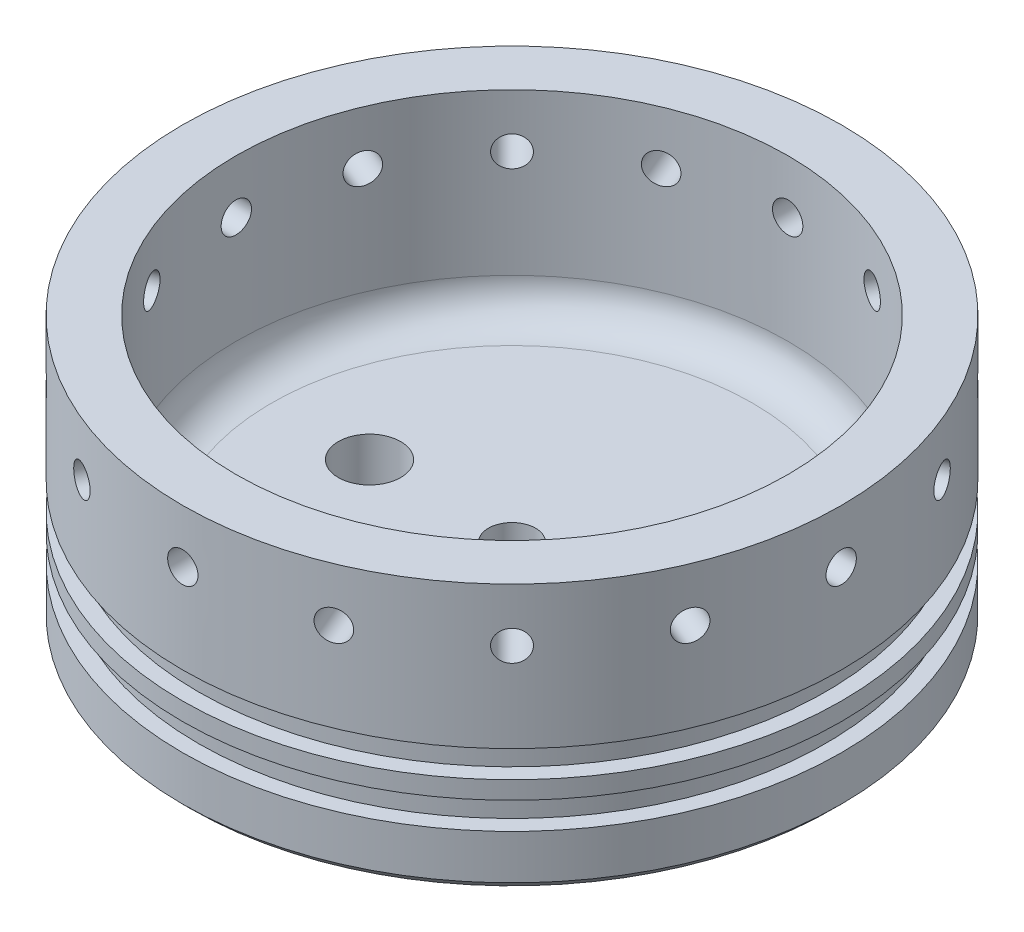
SolidWorks part; units mm, degrees
material "6061-T6 (SS)"
ref_plane "Front Plane" through (0, 0, 0) normal (0, 0, 1) x (1, 0, 0)
ref_plane "Top Plane" through (0, 0, 0) normal (0, 1, 0) x (1, 0, 0)
ref_plane "Right Plane" through (0, 0, 0) normal (1, 0, 0) x (0, 0, -1)
sketch "Sketch1" plane through (0, 0, 0) normal (0, 0, 1) x (1, 0, 0)
  line L1 (0, 0) -> (58.7375, 0)
  line L2 (58.7375, 0) -> (58.7375, 50.8) construction
  line L3 (0, 47.7012) -> (9.525, 47.7012)
  line L4 (58.7375, 0) -> (58.7375, 12.7)
  line L5 (58.7375, 12.7) -> (9.525, 12.7)
  line L6 (9.525, 12.7) -> (9.525, 47.7012)
  line L8 (0, 0) -> (0, 9.525)
  line L9 (0, 9.525) -> (2.8194, 9.525)
  line L10 (2.8194, 9.525) -> (2.8194, 14.3256)
  line L11 (2.8194, 14.3256) -> (0, 14.3256)
  line L15 (0, 14.3256) -> (0, 17.5006)
  line L16 (0, 17.5006) -> (2.8194, 17.5006)
  line L17 (2.8194, 17.5006) -> (2.8194, 22.3012)
  line L18 (2.8194, 22.3012) -> (0, 22.3012)
  line L19 (0, 22.3012) -> (0, 47.7012)
  point P13 (0, 0)
  dimension "D1" = 3.175
  dimension "D2" = 58.7375
  dimension "D3" = 12.7
  dimension "D4" = 9.525
  dimension "D5" = 4.8006
  dimension "D6" = 2.8194
  dimension "D10" = 25.4
  dimension "D11" = 9.525
revolve "Revolve1" add sketch "Sketch1" angle 360 about L2 region at (0.7567, 4.7625, 0)
ref_plane "HoleReferencePlane" through (0, 0, 58.7375) normal (0, 0, 1) x (1, 0, 0)
sketch "HoleReferencePoint" plane through (0, 0, 58.7375) normal (0, 0, 1) x (1, 0, 0)
  line L0 (107.95, 47.7012) -> (9.525, 47.7012) construction
  point P0 (58.7375, 38.1762)
  dimension "D1" = 9.525
hole_wizard "ForwardClosureHoles" positions "Sketch3" profile "Sketch5" hole size "1/4-28" standard "ANSI Inch" end condition through all
sketch "Sketch3" plane through (0, 0, 58.7375) normal (0, 0, 1) x (1, 0, 0)
  point P0 (58.7375, 38.1762)
sketch "Sketch5" plane through (58.7375, 38.1762, 58.7375) normal (1, 0, 0) x (0, -1, 0)
  line L0 (0, 0) -> (0, 117.475)
  line L1 (0, 117.475) -> (2.7051, 117.475)
  line L2 (2.7051, 117.475) -> (2.7051, 0)
  line L5 (2.7051, 0) -> (0, 0)
  line L11 (0, -6.35) -> (0, 107.95) construction
  dimension "Thru Hole Dia." = 5.4102
  dimension "Thru Hole Depth" = 117.475
sketch "Centerline" plane through (0, 0, 0) normal (0, 0, 1) x (1, 0, 0)
  line L0 (58.7375, 47.7012) -> (58.7375, 0) construction
  line L1 (117.475, 47.7012) -> (0, 47.7012) construction
  line L2 (0, 0) -> (117.475, 0) construction
pattern_circular "HolePattern" count 16 over 360 about axis through (58.7375, 47.7012, 0) along (0, -1, 0) of "ForwardClosureHoles"
ref_plane "HoleAlignmentPlane" through (0, 38.1762, 0) normal (0, 1, 0) x (1, 0, 0)
chamfer "Chamfer1" distance 1.5875 angle 45 1 edges at (58.7375, 0, -58.7375)
fillet "Fillet1" radius 6.35 1 edges at (58.7375, 12.7, -49.2125)
sketch "Sketch7" plane through (0, 0, 0) normal (0, 1, 0) x (1, 0, 0)
  line L0 (58.7375, 0) -> (84.1375, 0)
  line L2 (58.7375, 0) -> (33.3375, 0)
  point P2 (0, 0)
  point P4 (33.3375, 0)
  point P5 (58.7375, 0)
  dimension "D1" = 25.4
  dimension "D2" = 25.4
hole_wizard "Pipe Tap Drill for 1/8 Tap1" positions "Sketch8" profile "Sketch9" hole size "1/8" standard "ANSI Inch" end condition through all
sketch "Sketch8" plane through (0, 12.7, 0) normal (0, 1, 0) x (1, 0, 0)
  point P0 (58.7375, 0)
sketch "Sketch9" plane through (58.7375, 12.7, 0) normal (1, 0, 0) x (0, 0, 1)
  line L0 (0, 0) -> (0, 12.7)
  line L1 (0, 12.7) -> (4.2164, 12.7)
  line L2 (4.2164, 12.7) -> (4.2164, 0)
  line L5 (4.2164, 0) -> (0, 0)
  line L11 (0, -6.35) -> (0, 107.95) construction
  dimension "Thru Hole Dia." = 8.4328
  dimension "Thru Hole Depth" = 12.7
hole_wizard "Pipe Tap Drill for 1/16 Tap1" positions "Sketch10" profile "Sketch11" hole size "1/16" standard "ANSI Inch" end condition through all
sketch "Sketch10" plane through (0, 12.7, 0) normal (0, 1, 0) x (1, 0, 0)
  point P0 (84.1375, 0)
sketch "Sketch11" plane through (84.1375, 12.7, 0) normal (1, 0, 0) x (0, 0, 1)
  line L0 (0, 0) -> (0, 12.7)
  line L1 (0, 12.7) -> (3.0734, 12.7)
  line L2 (3.0734, 12.7) -> (3.0734, 0)
  line L5 (3.0734, 0) -> (0, 0)
  line L11 (0, -6.35) -> (0, 107.95) construction
  dimension "Thru Hole Dia." = 6.1468
  dimension "Thru Hole Depth" = 12.7
hole_wizard "Pipe Tap Drill for 1/4 Tap1" positions "Sketch13" profile "Sketch14" hole size "1/4" standard "ANSI Inch" end condition through all
sketch "Sketch13" plane through (0, 12.7, 0) normal (0, 1, 0) x (1, 0, 0)
  point P0 (33.3375, 0)
sketch "Sketch14" plane through (33.3375, 12.7, 0) normal (1, 0, 0) x (0, 0, 1)
  line L0 (0, 0) -> (0, 12.7)
  line L1 (0, 12.7) -> (5.5626, 12.7)
  line L2 (5.5626, 12.7) -> (5.5626, 0)
  line L5 (5.5626, 0) -> (0, 0)
  line L11 (0, -6.35) -> (0, 107.95) construction
  dimension "Thru Hole Dia." = 11.1252
  dimension "Thru Hole Depth" = 12.7
